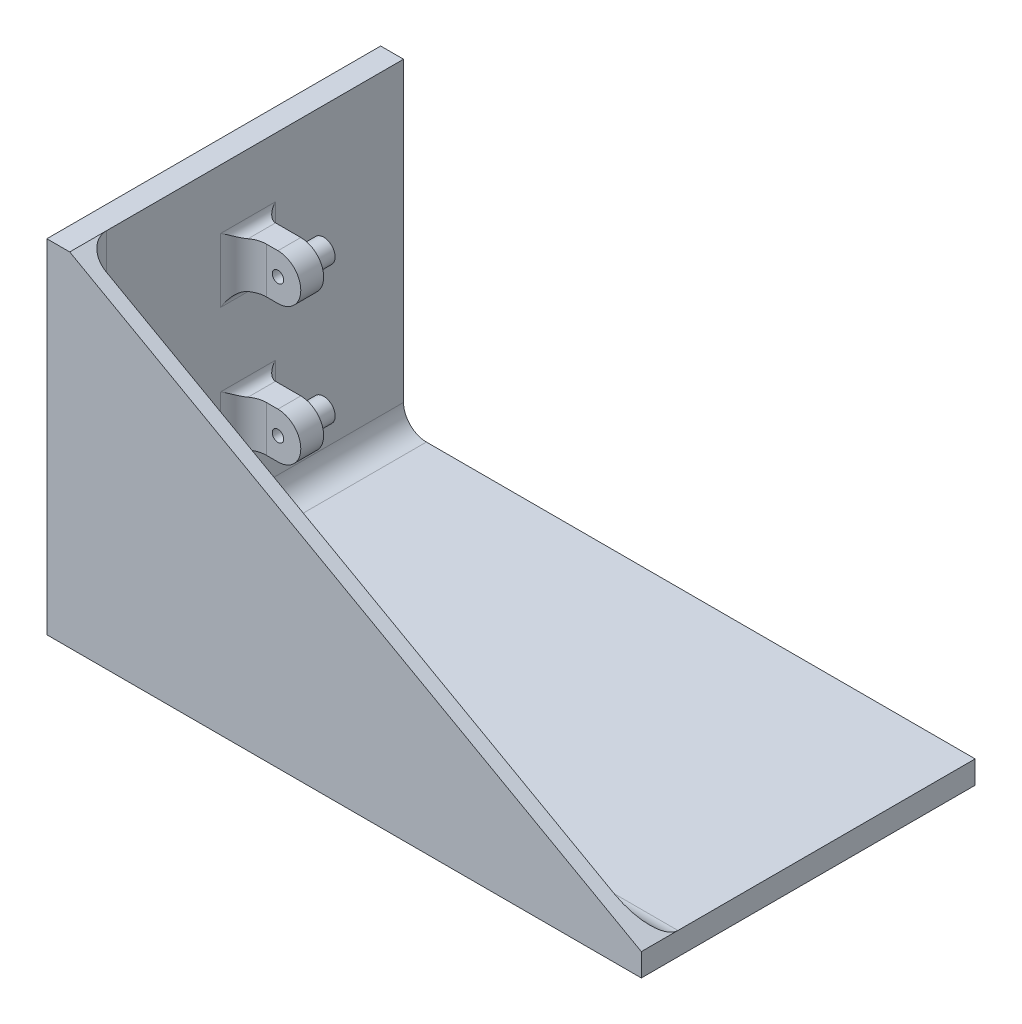
SolidWorks part; units mm, degrees
ref_plane "Piano frontale" through (0, 0, 0) normal (0, 0, 1) x (1, 0, 0)
ref_plane "Piano superiore" through (0, 0, 0) normal (0, 1, 0) x (1, 0, 0)
ref_plane "Piano destro" through (0, 0, 0) normal (1, 0, 0) x (0, 0, -1)
sketch "Schizzo1" plane through (0, 0, 0) normal (0, 0, 1) x (1, 0, 0)
  line L1 (0, 0) -> (-5, 0)
  line L2 (0, 0) -> (0, 70)
  line L3 (0, 70) -> (-5, 70)
  line L4 (-5, 0) -> (-5, 70)
  dimension "D1" = 70
  dimension "D2" = 5
extrude "Estrusione-Estrusione1" add sketch "Schizzo1" along normal blind 70
sketch "Schizzo2" plane through (0, 0, 70) normal (0, 0, 1) x (1, 0, 0)
  line L0 (0, 15) -> (0, 20)
  line L1 (0, 0) -> (0, 70) construction
  line L2 (0, 45) -> (0, 50)
  line L3 (7.5316, 55) -> (0, 55)
  line L4 (0, 55) -> (0, 45)
  line L5 (0, 45) -> (7.5316, 45)
  line L6 (7.5316, 25) -> (0, 25)
  line L7 (0, 25) -> (0, 15)
  line L8 (0, 15) -> (7.5316, 15)
  arc A0 (7.5316, 45) -> (7.5316, 55) centre (7.5316, 50) ccw
  arc A1 (7.5316, 15) -> (7.5316, 25) centre (7.5316, 20) ccw
  line M1 (0, 0) -> (0, 70)
  dimension "D1" = 10
  dimension "D2" = 10
extrude "Estrusione-Estrusione2" add sketch "Schizzo2" against normal blind 5 from offset 35 contours L5 A0 L3 M1 | L8 A1 L6 M1 region at (5.7836, 50, 70) region at (5.7836, 20, 70) offset against normal yes
sketch "Schizzo3" plane through (0, 0, 30) normal (0, 0, -1) x (-1, 0, 0)
  circle A0 centre (-7.5476, 50.0613) radius 2.5
  circle A1 centre (-7.5476, 19.9398) radius 2.5
  dimension "D1" = 5
  dimension "D2" = 5
extrude "Estrusione-Estrusione3" add sketch "Schizzo3" along normal blind 5
sketch "Schizzo4" plane through (0, 0, 0) normal (0, -1, 0) x (1, 0, 0)
  line L1 (-5, 0) -> (125, 0)
  line L2 (-5, 0) -> (-5, 70)
  line L3 (-5, 70) -> (125, 70)
  line L4 (125, 0) -> (125, 70)
extrude "Estrusione-Estrusione4" add sketch "Schizzo4" along normal blind 5
sketch "Schizzo5" plane through (0, 0, 25) normal (0, 0, -1) x (-1, 0, 0)
  circle A0 centre (-7.5476, 50.0613) radius 1.25
  circle A1 centre (-7.5476, 19.9398) radius 1.25
  dimension "D1" = 2.5
extrude "Taglio-Estrusione1" cut sketch "Schizzo5" against normal through all
sketch "Schizzo6" plane through (0, 0, 70) normal (0, 0, 1) x (1, 0, 0)
  line L0 (0, 70) -> (125, 0)
  line L7 (0, 0) -> (0, 70)
  line L8 (0, 70) -> (-5, 70)
  line L9 (-5, 70) -> (-5, -5)
  line L10 (-5, -5) -> (125, -5)
  line L11 (125, -5) -> (125, 0)
  line L12 (125, 0) -> (0, 0)
  line L13 (0, 0) -> (0, 70)
  line L14 (0, 70) -> (-5, 70)
  line L15 (-5, 70) -> (-5, -5)
  line L16 (-5, -5) -> (125, -5)
  line L17 (125, -5) -> (125, 0)
  line L18 (125, 0) -> (0, 0)
  line M7 (0, 0) -> (0, 70)
  line M8 (0, 70) -> (-5, 70)
  line M9 (-5, 70) -> (-5, -5)
  line M10 (-5, -5) -> (125, -5)
  line M11 (125, -5) -> (125, 0)
  line M12 (125, 0) -> (0, 0)
  dimension "D1" = 0
extrude "Estrusione-Estrusione5" add sketch "Schizzo6" along normal blind 3 contours M12 M7 M8 M9 M10 M11 | L0 M7 M12 region at (41.6667, 23.3333, 70) region at (-1.5008, 35, 70)
fillet "Raccordo1" radius 5 3 edges at (0, 0, 35) (0, 35, 70) (62.5, 0, 70)
fillet "Raccordo2" radius 5 2 edges at (0, 20, 35) (0, 50, 35)
fillet "Raccordo3" radius 2 2 edges at (0, 20, 30) (0, 50, 30)
fillet "Raccordo4" radius 2 4 edges at (0, 25, 34) (0, 15, 34) (0, 45, 34) (0, 55, 34)
